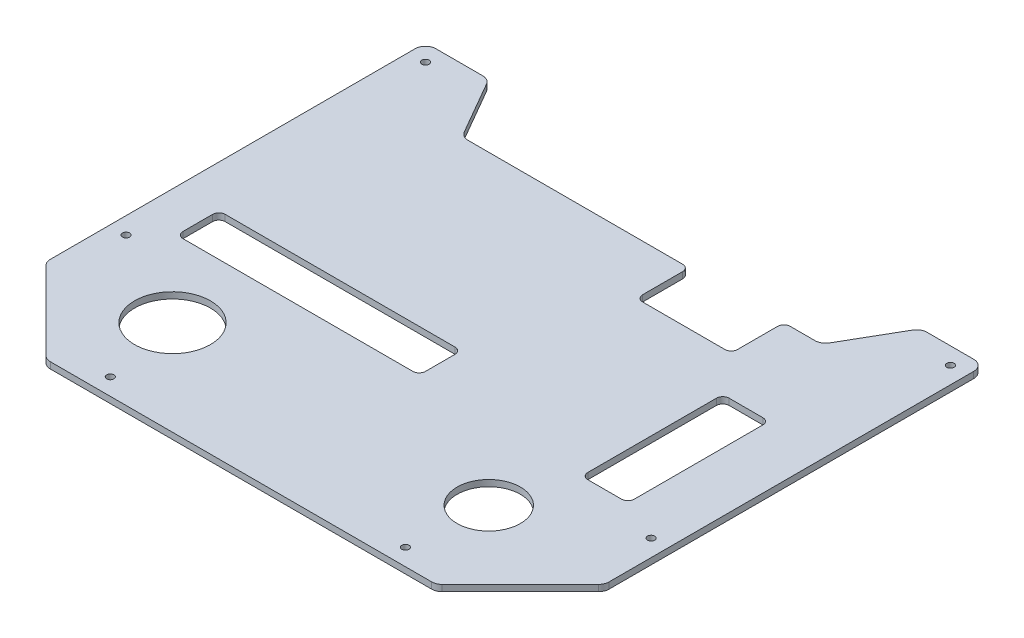
SolidWorks part; units mm, degrees
material "Acier non allié"
ref_plane "Front" through (0, 0, 0) normal (0, 0, 1) x (1, 0, 0)
ref_plane "Top" through (0, 0, 0) normal (0, 1, 0) x (1, 0, 0)
ref_plane "Right" through (0, 0, 0) normal (1, 0, 0) x (0, 0, -1)
sketch "Esquisse1" plane through (0, 0, 0) normal (0, 1, 0) x (1, 0, 0)
  line L0 (0, 0) -> (0, 1919.0564) construction
  line L1 (-92.5, 0) -> (92.5, 0)
  line L2 (92.5, 0) -> (132.5, 40)
  line L3 (132.5, 40) -> (132.5, 220)
  line L4 (132.5, 220) -> (102.5, 220)
  line L5 (102.5, 220) -> (85.1795, 190)
  line L6 (85.1795, 190) -> (-85.1795, 190)
  line L7 (-102.5, 220) -> (-85.1795, 190)
  line L8 (-132.5, 220) -> (-102.5, 220)
  line L9 (-132.5, 40) -> (-132.5, 220)
  line L10 (-92.5, 0) -> (-132.5, 40)
  point P12 (0, 190)
  dimension "D1" = 132.5
  dimension "D2" = 220
  dimension "D3" = 30
  dimension "D4" = 30
  dimension "D5" = 40
  dimension "D6" = 40
  dimension "D7" = 60
extrude "Boss.-Extru.1" add sketch "Esquisse1" along normal blind 3
fillet "Congé1" radius 5 10 edges at (132.5, 1.5, -220) (102.5, 1.5, -220) (85.1795, 1.5, -190) (-85.1795, 1.5, -190) (-102.5, 1.5, -220) (-132.5, 1.5, -220) (-132.5, 1.5, -40) (-92.5, 1.5, 0) (92.5, 1.5, 0) (132.5, 1.5, -40)
sketch "Esquisse2" plane through (0, 0, 0) normal (0, -1, 0) x (1, 0, 0)
  line L0 (0, 0) -> (0, -330.9968) construction
  line L1 (-90.4289, 0) -> (90.4289, 0) construction
  line L2 (-105.3868, -220) -> (-127.5, -220) construction
  line L3 (-132.5, -215) -> (-132.5, -42.0711) construction
  circle A0 centre (-70, -8) radius 1
  circle A1 centre (-124.5, -70) radius 1
  circle A2 centre (-124.5, -212) radius 1
  circle A3 centre (124.5, -212) radius 1
  circle A4 centre (124.5, -70) radius 1
  circle A5 centre (70, -8) radius 1
  dimension "D3" = 2
  dimension "D6" = 2
  dimension "D9" = 2
  dimension "D1" = 70
  dimension "D2" = 8
  dimension "D4" = 124.5
  dimension "D5" = 70
  dimension "D7" = 8
  dimension "D8" = 8
extrude "Enlèv. mat.-Extru.1" cut sketch "Esquisse2" against normal through all
hole_wizard "Dégagement M31" positions "Esquisse3" profile "Esquisse4" hole size "M3" standard "ISO" end condition through all
sketch "Esquisse3" plane through (0, 0, 0) normal (0, -1, 0) x (-1, 0, 0)
  point P0 (-70, 8)
  point P3 (-124.5, 70)
  point P6 (-124.5, 212)
  point P9 (124.5, 212)
  point P12 (124.5, 70)
  point P15 (70, 8)
sketch "Esquisse4" plane through (70, 0, -8) normal (1, 0, 0) x (0, 0, -1)
  line L0 (0, 0) -> (0, 3)
  line L1 (0, 3) -> (1.7, 3)
  line L2 (1.7, 3) -> (1.7, 0)
  line L5 (1.7, 0) -> (0, 0)
  line L11 (0, -6.35) -> (0, 107.95) construction
  dimension "Diamètre du perçage jusqu'au prochain" = 3.4
  dimension "Profondeur du perçage jusqu'au prochain" = 3
sketch "Esquisse5" plane through (0, 0, 0) normal (0, -1, 0) x (1, 0, 0)
  line L6 (82.2927, -190) -> (-82.2927, -190) construction
  line L7 (22.5, -190) -> (67.5, -190)
  line L20 (22.5, -190) -> (22.5, -165)
  line L21 (22.5, -165) -> (67.5, -165)
  line L22 (67.5, -190) -> (67.5, -165)
  line L23 (132.5, -42.0711) -> (132.5, -215) construction
  line L25 (-112.5, -102) -> (2.5, -102)
  line L26 (-112.5, -102) -> (-112.5, -82)
  line L27 (-112.5, -82) -> (2.5, -82)
  line L28 (2.5, -102) -> (2.5, -82)
  line L29 (-132.5, -215) -> (-132.5, -42.0711) construction
  line L30 (127.5, -220) -> (105.3868, -220) construction
  line L31 (82.5, -146) -> (104.5, -146)
  line L32 (82.5, -146) -> (82.5, -79)
  line L33 (82.5, -79) -> (104.5, -79)
  line L34 (104.5, -146) -> (104.5, -79)
  line L35 (-90.4289, 0) -> (90.4289, 0) construction
  circle A0 centre (-77.5, -45) radius 18
  circle A1 centre (72.5, -45) radius 15
  dimension "D14" = 36
  dimension "D17" = 30
  dimension "D1" = 65
  dimension "D2" = 110
  dimension "D3" = 25
  dimension "D4" = 82
  dimension "D5" = 135
  dimension "D6" = 20
  dimension "D7" = 115
  dimension "D8" = 50
  dimension "D9" = 74
  dimension "D10" = 67
  dimension "D11" = 22
  dimension "D12" = 55
  dimension "D13" = 45
  dimension "D15" = 60
  dimension "D16" = 45
extrude "Enlèv. mat.-Extru.2" cut sketch "Esquisse5" against normal through all
fillet "Congé2" radius 3 12 edges at (67.5, 1.5, -190) (67.5, 1.5, -165) (22.5, 1.5, -165) (22.5, 1.5, -190) (104.5, 1.5, -146) (82.5, 1.5, -146) (82.5, 1.5, -79) (104.5, 1.5, -79) (2.5, 1.5, -82) (2.5, 1.5, -102) (-112.5, 1.5, -82) (-112.5, 1.5, -102)
equation "\"WIDTH\"= 300mm'Total width of the robot"
equation "\"LENGTH\"= 220mm'Total length of the robot"
equation "\"CUT_DEPTH\"= 45mm'Depth of the cut on the edges of the plate"
equation "\"Plate_th\"= 3mm'Thickness of the plate"
equation "\"D1\"= \"Plate_th\""
